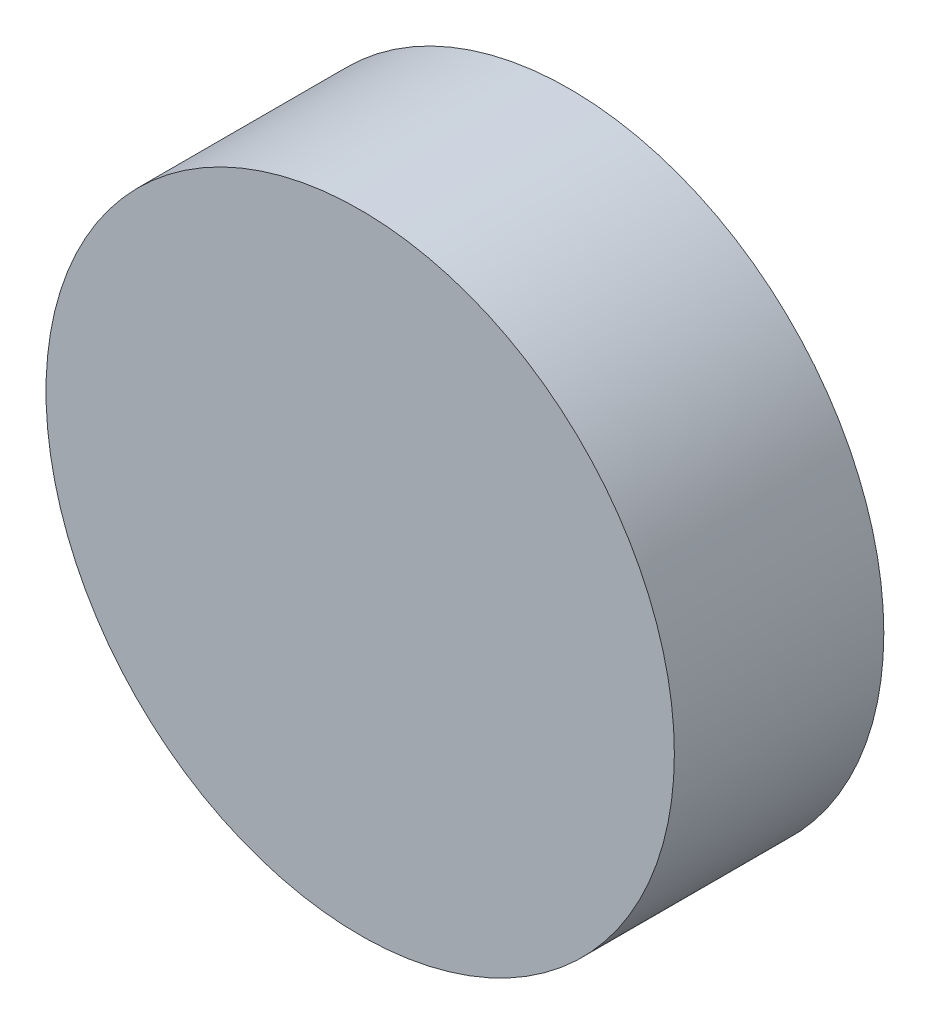
SolidWorks part; units mm, degrees
ref_plane "前视基准面" through (0, 0, 0) normal (0, 0, 1) x (1, 0, 0)
ref_plane "上视基准面" through (0, 0, 0) normal (0, 1, 0) x (1, 0, 0)
ref_plane "右视基准面" through (0, 0, 0) normal (1, 0, 0) x (0, 0, -1)
sketch "草图1" plane through (0, 0, 0) normal (0, 0, 1) x (1, 0, 0)
  circle A0 centre (0, 0) radius 15
extrude "凸台-拉伸1" add sketch "草图1" along normal blind 10
ref_point "点2"
ref_point "点4"
sketch "草图2" plane through (0, 0, 10) normal (0, 0, 1) x (1, 0, 0)
  line L0 (0, 0) -> (0, 15)
  circle A0 centre (0, 0) radius 15 construction
sketch "草图3" plane through (0, 0, 0) normal (0, 0, -1) x (-1, 0, 0)
  line L0 (0, 0) -> (0, 15)
ref_axis "基准轴1" through (0, 0, 0) along (0, 0, -1)
ref_axis "基准轴2" through (0, 0, 10) along (0, 0, 1)
ref_axis "基准轴3" through (0, 0, 10) along (0, 1, 0)
ref_axis "基准轴4" through (0, 0, 0) along (0, 1, 0)
